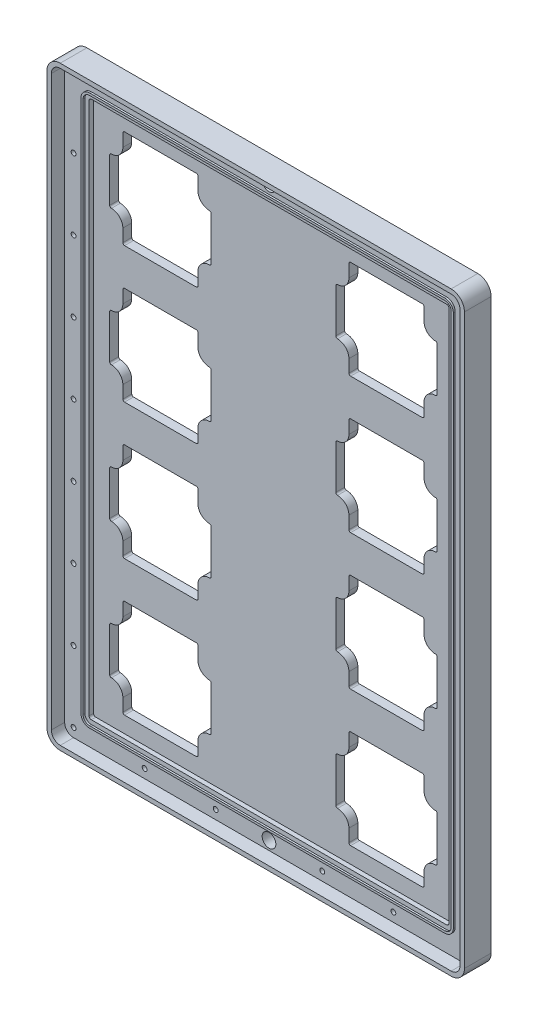
SolidWorks part; units mm, degrees
ref_plane "Front Plane" through (0, 0, 0) normal (0, 0, 1) x (1, 0, 0)
ref_plane "Top Plane" through (0, 0, 0) normal (0, 1, 0) x (1, 0, 0)
ref_plane "Right Plane" through (0, 0, 0) normal (1, 0, 0) x (0, 0, -1)
sketch "Sketch1" plane through (0, 0, 0) normal (0, 0, 1) x (1, 0, 0)
  line L1 (0, 0) -> (292.1, 0)
  line L2 (0, 0) -> (0, 419.1)
  line L3 (0, 419.1) -> (292.1, 419.1)
  line L4 (292.1, 0) -> (292.1, 419.1)
  dimension "D1" = 419.1
  dimension "D2" = 292.1
extrude "Boss-Extrude1" add sketch "Sketch1" along normal blind 9.525
sketch "Sketch4" plane through (0, 0, 9.525) normal (0, 0, 1) x (1, 0, 0)
  line L3 (0, 419.1) -> (0, 0) construction
  line L4 (6.35, 412.75) -> (285.75, 412.75) construction
  line L5 (6.35, 412.75) -> (6.35, 6.35) construction
  line L6 (6.35, 6.35) -> (285.75, 6.35) construction
  line L7 (285.75, 412.75) -> (285.75, 6.35) construction
  line L8 (292.1, 419.1) -> (0, 419.1) construction
  line L9 (292.1, 0) -> (292.1, 419.1) construction
  line L10 (0, 0) -> (292.1, 0) construction
  circle A0 centre (6.35, 6.35) radius 1.7272
  circle A1 centre (6.35, 412.75) radius 1.7272
  circle A2 centre (285.75, 412.75) radius 1.7272
  circle A3 centre (285.75, 6.35) radius 1.7272
  dimension "D5" = 3.4544
  dimension "D1" = 6.35
  dimension "D2" = 6.35
  dimension "D3" = 6.35
  dimension "D4" = 6.35
extrude "Cut-Extrude1" cut sketch "Sketch4" against normal blind 7.62
pattern_linear "LPattern2" count 8 spacing 50.8 along (0, -1, 0) of "Cut-Extrude1"
sketch "Sketch5" plane through (0, 0, 9.525) normal (0, 0, 1) x (1, 0, 0)
  line L0 (0, 419.1) -> (0, 0) construction
  line L1 (19.05, 406.4) -> (273.05, 406.4) construction
  line L2 (12.7, 400.05) -> (12.7, 19.05) construction
  line L3 (19.05, 12.7) -> (273.05, 12.7) construction
  line L4 (279.4, 400.05) -> (279.4, 19.05) construction
  line L5 (292.1, 419.1) -> (0, 419.1) construction
  line L6 (292.1, 0) -> (292.1, 419.1) construction
  line L7 (0, 0) -> (292.1, 0) construction
  line L8 (19.05, 14.732) -> (273.05, 14.732) construction
  line L9 (14.732, 400.05) -> (14.732, 19.05) construction
  line L10 (19.05, 404.368) -> (273.05, 404.368) construction
  line L11 (277.368, 400.05) -> (277.368, 19.05) construction
  line L12 (12.954, 400.05) -> (12.954, 19.05)
  line L13 (19.05, 406.146) -> (273.05, 406.146)
  line L14 (279.146, 400.05) -> (279.146, 19.05)
  line L15 (19.05, 12.954) -> (273.05, 12.954)
  line L16 (277.622, 400.05) -> (277.622, 19.05)
  line L17 (19.05, 404.622) -> (273.05, 404.622)
  line L18 (14.478, 400.05) -> (14.478, 19.05)
  line L19 (19.05, 14.478) -> (273.05, 14.478)
  arc A0 (273.05, 12.7) -> (279.4, 19.05) centre (273.05, 19.05) ccw construction
  arc A1 (12.7, 19.05) -> (19.05, 12.7) centre (19.05, 19.05) ccw construction
  arc A2 (273.05, 406.4) -> (279.4, 400.05) centre (273.05, 400.05) cw construction
  arc A3 (19.05, 406.4) -> (12.7, 400.05) centre (19.05, 400.05) ccw construction
  arc A4 (14.732, 19.05) -> (19.05, 14.732) centre (19.05, 19.05) ccw construction
  arc A5 (19.05, 404.368) -> (14.732, 400.05) centre (19.05, 400.05) ccw construction
  arc A6 (273.05, 404.368) -> (277.368, 400.05) centre (273.05, 400.05) cw construction
  arc A7 (273.05, 14.732) -> (277.368, 19.05) centre (273.05, 19.05) ccw construction
  arc A8 (19.05, 406.146) -> (12.954, 400.05) centre (19.05, 400.05) ccw
  arc A9 (273.05, 406.146) -> (279.146, 400.05) centre (273.05, 400.05) cw
  arc A10 (273.05, 12.954) -> (279.146, 19.05) centre (273.05, 19.05) ccw
  arc A11 (12.954, 19.05) -> (19.05, 12.954) centre (19.05, 19.05) ccw
  arc A12 (273.05, 404.622) -> (277.622, 400.05) centre (273.05, 400.05) cw
  arc A13 (19.05, 404.622) -> (14.478, 400.05) centre (19.05, 400.05) ccw
  arc A14 (14.478, 19.05) -> (19.05, 14.478) centre (19.05, 19.05) ccw
  arc A15 (273.05, 14.478) -> (277.622, 19.05) centre (273.05, 19.05) ccw
  dimension "D5" = 6.35
  dimension "D1" = 12.7
  dimension "D2" = 12.7
  dimension "D3" = 12.7
  dimension "D4" = 12.7
  dimension "D6" = 2.032
  dimension "D7" = 2.032
  dimension "D8" = 0.254
  dimension "D9" = 0.254
  dimension "D10" = 0.254
sketch "Sketch6" plane through (0, 0, 9.525) normal (0, 0, 1) x (1, 0, 0)
  line L0 (292.1, 419.1) -> (0, 419.1) construction
  line L1 (0, 419.1) -> (0, 0) construction
  line L24 (273.05, 401.6375) -> (19.05, 401.6375)
  line L25 (274.6375, 19.05) -> (274.6375, 400.05)
  line L26 (19.05, 17.4625) -> (273.05, 17.4625)
  line L27 (17.4625, 400.05) -> (17.4625, 19.05)
  line L28 (273.05, 401.6375) -> (19.05, 401.6375)
  line L29 (274.6375, 19.05) -> (274.6375, 400.05)
  line L30 (19.05, 17.4625) -> (273.05, 17.4625)
  line L31 (17.4625, 400.05) -> (17.4625, 19.05)
  arc A20 (19.05, 401.6375) -> (17.4625, 400.05) centre (19.05, 400.05) ccw
  arc A21 (274.6375, 400.05) -> (273.05, 401.6375) centre (273.05, 400.05) ccw
  arc A22 (273.05, 17.4625) -> (274.6375, 19.05) centre (273.05, 19.05) ccw
  arc A23 (17.4625, 19.05) -> (19.05, 17.4625) centre (19.05, 19.05) ccw
  arc A24 (19.05, 401.6375) -> (17.4625, 400.05) centre (19.05, 400.05) ccw
  arc A25 (274.6375, 400.05) -> (273.05, 401.6375) centre (273.05, 400.05) ccw
  arc A26 (273.05, 17.4625) -> (274.6375, 19.05) centre (273.05, 19.05) ccw
  arc A27 (17.4625, 19.05) -> (19.05, 17.4625) centre (19.05, 19.05) ccw
  dimension "D2" = 17.4625
  dimension "D3" = 17.4625
  dimension "D1" = 2.7305
extrude "Cut-Extrude3" cut sketch "Sketch6" against normal blind 3.175
extrude "Boss-Extrude2" add sketch "Sketch5" along normal blind 1.3335 contours L12 A11 L15 A10 L14 A9 L13 A8 A15 L19 A14 L18 A13 L17 A12 L16 region at (15.0752, 404.0248, 9.525)
fillet "Fillet1" radius 6.35 4 edges at (0, 419.1, 4.7625) (292.1, 419.1, 4.7625) (0, 0, 4.7625) (292.1, 0, 4.7625)
sketch "Sketch8" plane through (0, 0, 0) normal (0, 0, -1) x (-1, 0, 0)
  line L0 (-264.668, 370.459) -> (-264.668, 339.2678)
  line L1 (-255.27, 329.8698) -> (-255.27, 320.8782)
  line L2 (-252.4506, 318.0588) -> (-201.2442, 318.0588)
  line L3 (-198.4248, 320.8782) -> (-198.4248, 329.8698)
  line L4 (-189.0268, 339.2678) -> (-189.0268, 370.459)
  line L5 (-198.4248, 379.857) -> (-198.4248, 388.8486)
  line L6 (-201.2442, 391.668) -> (-252.4506, 391.668)
  line L7 (-255.27, 388.8486) -> (-255.27, 379.857)
  line L8 (-261.8486, 391.668) -> (-261.8486, 318.0588) construction
  line L9 (-264.668, 388.8486) -> (-189.0268, 388.8486) construction
  line L10 (-264.668, 391.668) -> (-189.0268, 391.668) construction
  line L11 (-264.668, 391.668) -> (-264.668, 318.0588) construction
  line L12 (-264.668, 318.0588) -> (-189.0268, 318.0588) construction
  line L13 (-189.0268, 391.668) -> (-189.0268, 318.0588) construction
  line L14 (-264.668, 379.857) -> (-189.0268, 379.857) construction
  line L15 (-264.668, 370.459) -> (-189.0268, 370.459) construction
  line L16 (-264.668, 339.2678) -> (-189.0268, 339.2678) construction
  line L17 (-264.668, 329.8698) -> (-189.0268, 329.8698) construction
  line L18 (-264.668, 320.8782) -> (-189.0268, 320.8782) construction
  line L19 (-255.27, 318.0588) -> (-255.27, 391.668) construction
  line L20 (-252.4506, 391.668) -> (-252.4506, 318.0588) construction
  line L21 (-201.2442, 391.668) -> (-201.2442, 318.0588) construction
  line L22 (-198.4248, 391.668) -> (-198.4248, 318.0588) construction
  line L23 (-191.8462, 318.0588) -> (-191.8462, 391.668) construction
  line L24 (-189.0268, 373.2784) -> (-264.668, 373.2784) construction
  line L27 (-201.2442, 393.7) -> (-252.4506, 393.7)
  line L28 (-257.302, 388.8486) -> (-257.302, 379.857)
  line L29 (-266.7, 370.459) -> (-266.7, 339.2678)
  line L30 (-257.302, 329.8698) -> (-257.302, 320.8782)
  line L31 (-252.4506, 316.0268) -> (-201.2442, 316.0268)
  line L32 (-196.3928, 320.8782) -> (-196.3928, 329.8698)
  line L33 (-186.9948, 339.2678) -> (-186.9948, 370.459)
  line L34 (-196.3928, 379.857) -> (-196.3928, 388.8486)
  line L35 (-285.75, 419.1) -> (-6.35, 419.1) construction
  line L36 (-292.1, 6.35) -> (-292.1, 412.75) construction
  arc A0 (-261.8486, 373.2784) -> (-255.27, 379.857) centre (-261.8486, 379.857) ccw
  arc A1 (-261.8486, 373.2784) -> (-264.668, 370.459) centre (-261.8486, 370.459) ccw
  arc A2 (-264.668, 339.2678) -> (-261.8486, 336.4484) centre (-261.8486, 339.2678) ccw
  arc A3 (-255.27, 329.8698) -> (-261.8486, 336.4484) centre (-261.8486, 329.8698) ccw
  arc A4 (-255.27, 320.8782) -> (-252.4506, 318.0588) centre (-252.4506, 320.8782) ccw
  arc A5 (-201.2442, 318.0588) -> (-198.4248, 320.8782) centre (-201.2442, 320.8782) ccw
  arc A6 (-191.8462, 336.4484) -> (-198.4248, 329.8698) centre (-191.8462, 329.8698) ccw
  arc A7 (-191.8462, 336.4484) -> (-189.0268, 339.2678) centre (-191.8462, 339.2678) ccw
  arc A8 (-189.0268, 370.459) -> (-191.8462, 373.2784) centre (-191.8462, 370.459) ccw
  arc A9 (-198.4248, 379.857) -> (-191.8462, 373.2784) centre (-191.8462, 379.857) ccw
  arc A10 (-198.4248, 388.8486) -> (-201.2442, 391.668) centre (-201.2442, 388.8486) ccw
  arc A11 (-252.4506, 391.668) -> (-255.27, 388.8486) centre (-252.4506, 388.8486) ccw
  arc A12 (-252.4506, 393.7) -> (-257.302, 388.8486) centre (-252.4506, 388.8486) ccw
  arc A13 (-261.8486, 375.3104) -> (-257.302, 379.857) centre (-261.8486, 379.857) ccw
  arc A14 (-261.8486, 375.3104) -> (-266.7, 370.459) centre (-261.8486, 370.459) ccw
  arc A15 (-266.7, 339.2678) -> (-261.8486, 334.4164) centre (-261.8486, 339.2678) ccw
  arc A16 (-257.302, 329.8698) -> (-261.8486, 334.4164) centre (-261.8486, 329.8698) ccw
  arc A17 (-257.302, 320.8782) -> (-252.4506, 316.0268) centre (-252.4506, 320.8782) ccw
  arc A18 (-201.2442, 316.0268) -> (-196.3928, 320.8782) centre (-201.2442, 320.8782) ccw
  arc A19 (-191.8462, 334.4164) -> (-196.3928, 329.8698) centre (-191.8462, 329.8698) ccw
  arc A20 (-191.8462, 334.4164) -> (-186.9948, 339.2678) centre (-191.8462, 339.2678) ccw
  arc A21 (-186.9948, 370.459) -> (-191.8462, 375.3104) centre (-191.8462, 370.459) ccw
  arc A22 (-196.3928, 379.857) -> (-191.8462, 375.3104) centre (-191.8462, 379.857) ccw
  arc A23 (-196.3928, 388.8486) -> (-201.2442, 393.7) centre (-201.2442, 388.8486) ccw
  dimension "D4" = 11.811
  dimension "D5" = 21.209
  dimension "D6" = 52.4002
  dimension "D1" = 73.6092
  dimension "D2" = 75.6412
  dimension "D3" = 2.8194
  dimension "D7" = 61.7982
  dimension "D8" = 70.7898
  dimension "D9" = 2.8194
  dimension "D10" = 9.398
  dimension "D11" = 12.2174
  dimension "D12" = 63.4238
  dimension "D13" = 66.2432
  dimension "D14" = 72.8218
  dimension "D15" = 55.2196
  dimension "D16" = 25.4
  dimension "D17" = 25.4
  dimension "D18" = 2.032
extrude "Cut-Extrude5" cut sketch "Sketch8" against normal blind 3.175
sketch "Sketch10" plane through (0, 0, 0) normal (0, 0, -1) x (-1, 0, 0)
  line L18 (-263.0805, 370.459) -> (-263.0805, 339.2678)
  line L19 (-253.6825, 329.8698) -> (-253.6825, 320.8782)
  line L20 (-252.4506, 319.6463) -> (-201.2442, 319.6463)
  line L21 (-200.0123, 320.8782) -> (-200.0123, 329.8698)
  line L22 (-190.6143, 339.2678) -> (-190.6143, 370.459)
  line L23 (-200.0123, 379.857) -> (-200.0123, 388.8486)
  line L24 (-201.2442, 390.0805) -> (-252.4506, 390.0805)
  line L25 (-253.6825, 388.8486) -> (-253.6825, 379.857)
  line L26 (-263.0805, 370.459) -> (-263.0805, 339.2678)
  line L27 (-253.6825, 329.8698) -> (-253.6825, 320.8782)
  line L28 (-252.4506, 319.6463) -> (-201.2442, 319.6463)
  line L29 (-200.0123, 320.8782) -> (-200.0123, 329.8698)
  line L30 (-190.6143, 339.2678) -> (-190.6143, 370.459)
  line L31 (-200.0123, 379.857) -> (-200.0123, 388.8486)
  line L32 (-201.2442, 390.0805) -> (-252.4506, 390.0805)
  line L33 (-253.6825, 388.8486) -> (-253.6825, 379.857)
  arc A28 (-261.8486, 371.6909) -> (-263.0805, 370.459) centre (-261.8486, 370.459) ccw
  arc A29 (-263.0805, 339.2678) -> (-261.8486, 338.0359) centre (-261.8486, 339.2678) ccw
  arc A30 (-253.6825, 329.8698) -> (-261.8486, 338.0359) centre (-261.8486, 329.8698) ccw
  arc A31 (-253.6825, 320.8782) -> (-252.4506, 319.6463) centre (-252.4506, 320.8782) ccw
  arc A32 (-201.2442, 319.6463) -> (-200.0123, 320.8782) centre (-201.2442, 320.8782) ccw
  arc A33 (-191.8462, 338.0359) -> (-200.0123, 329.8698) centre (-191.8462, 329.8698) ccw
  arc A34 (-191.8462, 338.0359) -> (-190.6143, 339.2678) centre (-191.8462, 339.2678) ccw
  arc A35 (-190.6143, 370.459) -> (-191.8462, 371.6909) centre (-191.8462, 370.459) ccw
  arc A36 (-200.0123, 379.857) -> (-191.8462, 371.6909) centre (-191.8462, 379.857) ccw
  arc A37 (-200.0123, 388.8486) -> (-201.2442, 390.0805) centre (-201.2442, 388.8486) ccw
  arc A38 (-252.4506, 390.0805) -> (-253.6825, 388.8486) centre (-252.4506, 388.8486) ccw
  arc A39 (-261.8486, 371.6909) -> (-253.6825, 379.857) centre (-261.8486, 379.857) ccw
  arc A40 (-261.8486, 371.6909) -> (-263.0805, 370.459) centre (-261.8486, 370.459) ccw
  arc A41 (-263.0805, 339.2678) -> (-261.8486, 338.0359) centre (-261.8486, 339.2678) ccw
  arc A42 (-253.6825, 329.8698) -> (-261.8486, 338.0359) centre (-261.8486, 329.8698) ccw
  arc A43 (-253.6825, 320.8782) -> (-252.4506, 319.6463) centre (-252.4506, 320.8782) ccw
  arc A44 (-201.2442, 319.6463) -> (-200.0123, 320.8782) centre (-201.2442, 320.8782) ccw
  arc A45 (-191.8462, 338.0359) -> (-200.0123, 329.8698) centre (-191.8462, 329.8698) ccw
  arc A46 (-191.8462, 338.0359) -> (-190.6143, 339.2678) centre (-191.8462, 339.2678) ccw
  arc A47 (-190.6143, 370.459) -> (-191.8462, 371.6909) centre (-191.8462, 370.459) ccw
  arc A48 (-200.0123, 379.857) -> (-191.8462, 371.6909) centre (-191.8462, 379.857) ccw
  arc A49 (-200.0123, 388.8486) -> (-201.2442, 390.0805) centre (-201.2442, 388.8486) ccw
  arc A50 (-252.4506, 390.0805) -> (-253.6825, 388.8486) centre (-252.4506, 388.8486) ccw
  arc A51 (-261.8486, 371.6909) -> (-253.6825, 379.857) centre (-261.8486, 379.857) ccw
  dimension "D1" = 1.5875
extrude "Cut-Extrude6" cut sketch "Sketch10" against normal through all
sketch "Sketch11" plane through (0, 0, 0) normal (0, 0, -1) x (-1, 0, 0)
  line L0 (-226.8474, 388.8994) -> (-226.8474, 393.7) construction
  line L1 (-261.8486, 388.8994) -> (-191.8462, 388.8994) construction
  line L2 (-261.8486, 388.8994) -> (-261.8486, 320.8274) construction
  line L3 (-261.8486, 320.8274) -> (-191.8462, 320.8274) construction
  line L4 (-191.8462, 388.8994) -> (-191.8462, 320.8274) construction
  line L5 (-201.2442, 393.7) -> (-252.4506, 393.7) construction
  line L6 (-226.8474, 320.8274) -> (-226.8474, 316.0268) construction
  line L7 (-252.4506, 316.0268) -> (-201.2442, 316.0268) construction
  line L8 (-261.8486, 354.8634) -> (-266.7, 354.8634) construction
  line L9 (-266.7, 370.459) -> (-266.7, 339.2678) construction
  line L10 (-191.8462, 354.8634) -> (-186.9948, 354.8634) construction
  line L11 (-186.9948, 339.2678) -> (-186.9948, 370.459) construction
  circle A0 centre (-261.8486, 388.8994) radius 1.1303
  circle A1 centre (-191.8462, 388.8994) radius 1.1303
  circle A2 centre (-191.8462, 320.8274) radius 1.1303
  circle A3 centre (-261.8486, 320.8274) radius 1.1303
  dimension "D3" = 2.2606
  dimension "D1" = 70.0024
  dimension "D2" = 68.072
extrude "Cut-Extrude7" cut sketch "Sketch11" against normal blind 3.9688
pattern_linear "LPattern1" count 2 spacing 161.5948 along (-1, 0, 0) count 4 spacing 96.8756 along (0, -1, 0) of "Cut-Extrude6", "Cut-Extrude5", "Cut-Extrude7"
sketch "Sketch13" plane through (0, 0, 0) normal (0, 0, -1) x (-1, 0, 0)
  line L4 (-6.35, 419.1) -> (-285.75, 419.1)
  line L5 (-292.1, 412.75) -> (-292.1, 6.35)
  line L6 (-285.75, 0) -> (-6.35, 0)
  line L7 (0, 6.35) -> (0, 412.75)
  line L8 (-285.75, -3.175) -> (-6.35, -3.175)
  line L9 (3.175, 6.35) -> (3.175, 412.75)
  line L10 (-6.35, 422.275) -> (-285.75, 422.275)
  line L11 (-295.275, 412.75) -> (-295.275, 6.35)
  line L12 (-285.75, -3.175) -> (-6.35, -3.175)
  line L13 (3.175, 6.35) -> (3.175, 412.75)
  line L14 (-6.35, 422.275) -> (-285.75, 422.275)
  line L15 (-295.275, 412.75) -> (-295.275, 6.35)
  arc A4 (-285.75, 419.1) -> (-292.1, 412.75) centre (-285.75, 412.75) ccw
  arc A5 (-292.1, 6.35) -> (-285.75, 0) centre (-285.75, 6.35) ccw
  arc A6 (-6.35, 0) -> (0, 6.35) centre (-6.35, 6.35) ccw
  arc A7 (0, 412.75) -> (-6.35, 419.1) centre (-6.35, 412.75) ccw
  arc A8 (-295.275, 6.35) -> (-285.75, -3.175) centre (-285.75, 6.35) ccw
  arc A9 (-6.35, -3.175) -> (3.175, 6.35) centre (-6.35, 6.35) ccw
  arc A10 (3.175, 412.75) -> (-6.35, 422.275) centre (-6.35, 412.75) ccw
  arc A11 (-285.75, 422.275) -> (-295.275, 412.75) centre (-285.75, 412.75) ccw
  arc A12 (-295.275, 6.35) -> (-285.75, -3.175) centre (-285.75, 6.35) ccw
  arc A13 (-6.35, -3.175) -> (3.175, 6.35) centre (-6.35, 6.35) ccw
  arc A14 (3.175, 412.75) -> (-6.35, 422.275) centre (-6.35, 412.75) ccw
  arc A15 (-285.75, 422.275) -> (-295.275, 412.75) centre (-285.75, 412.75) ccw
  dimension "D1" = 3.175
  dimension "D2" = 3.175
extrude "Boss-Extrude5" add sketch "Sketch13" against normal blind 19.05
sketch "Sketch14" plane through (0, 0, 9.525) normal (0, 0, 1) x (1, 0, 0)
  line L0 (285.75, 6.35) -> (6.35, 6.35) construction
  circle A0 centre (234.95, 6.35) radius 1.7272
  circle A1 centre (184.15, 6.35) radius 1.7272
  circle A2 centre (107.95, 6.35) radius 1.7272
  circle A3 centre (57.15, 6.35) radius 1.7272
  circle A4 centre (6.35, 6.35) radius 1.7272 construction
  dimension "D1" = 50.8
  dimension "D2" = 50.8
  dimension "D3" = 50.8
  dimension "D4" = 50.8
extrude "Cut-Extrude8" cut sketch "Sketch14" against normal blind 7.62
sketch "Sketch15" plane through (0, 0, 9.525) normal (0, 0, 1) x (1, 0, 0)
  line L0 (285.75, 6.35) -> (6.35, 6.35) construction
  circle A0 centre (146.05, 6.35) radius 4.9022
  dimension "D1" = 9.8044
extrude "Cut-Extrude9" cut sketch "Sketch15" against normal through all
pattern_linear "LPattern3" count 2 spacing 406.4 along (0, 1, 0) of "Cut-Extrude8", "Cut-Extrude9"
